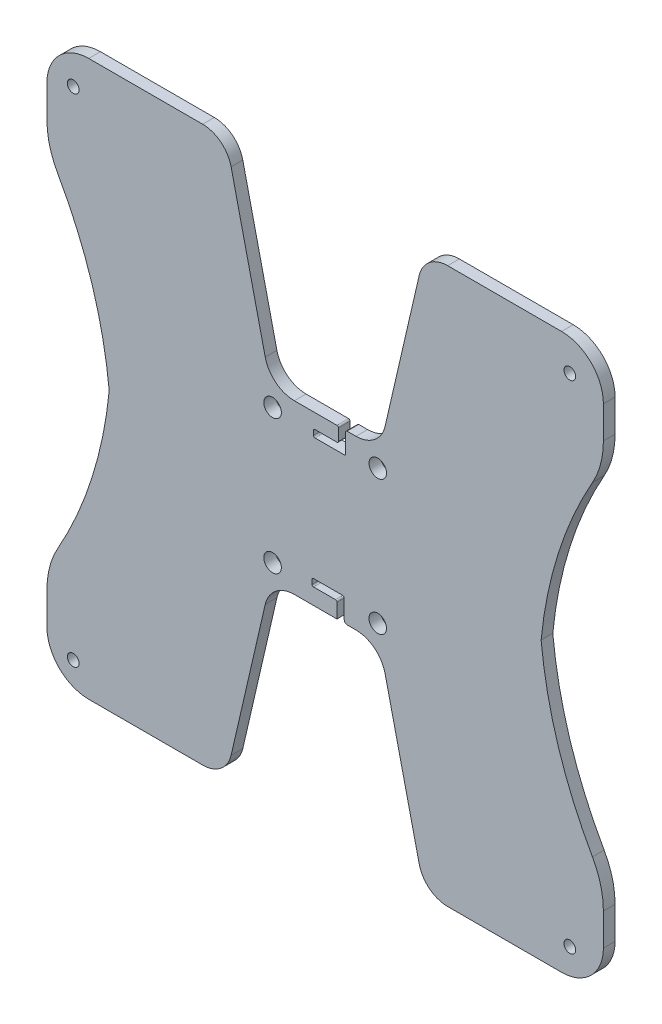
SolidWorks part; units mm, degrees
ref_plane "Front Plane" through (0, 0, 0) normal (0, 0, 1) x (1, 0, 0)
ref_plane "Top Plane" through (0, 0, 0) normal (0, 1, 0) x (1, 0, 0)
ref_plane "Right Plane" through (0, 0, 0) normal (1, 0, 0) x (0, 0, -1)
sketch "Sketch2" plane through (0, 0, 0) normal (0, 0, 1) x (1, 0, 0)
  line L3 (94.3754, -52.7044) -> (94.3754, -56.7044)
  line L4 (93.8754, -57.2044) -> (86.3754, -57.2044)
  line L5 (85.8754, -57.7044) -> (85.8754, -59.2044)
  line L6 (86.3754, -59.7044) -> (96.3754, -59.7044)
  line L7 (96.8754, -59.2044) -> (96.8754, -52.7044)
  line L8 (97.3754, -52.2044) -> (100.3754, -52.2044)
  line L9 (110.3627, -44.2602) -> (122.0425, 6.3307)
  line L10 (131.7862, 14.0812) -> (170.7845, 14.0812)
  line L11 (185.0955, -0.2297) -> (185.0955, -11.2297)
  line L16 (96.3754, -108.6331) -> (96.3754, -102.1331)
  line L17 (95.8754, -101.6331) -> (85.8754, -101.6331)
  line L18 (85.3754, -102.1331) -> (85.3754, -103.6331)
  line L19 (85.8754, -104.1331) -> (93.3754, -104.1331)
  line L20 (93.8754, -104.6331) -> (93.8754, -108.6331)
  line L26 (163.7717, -80.9188) -> (-81.9172, -80.9188) construction
  line L27 (97.3754, -109.6331) -> (100.3754, -109.6331)
  line L28 (185.0955, -161.6078) -> (185.0955, -150.6078)
  line L29 (131.7862, -175.9188) -> (170.7845, -175.9188)
  line L30 (110.3627, -117.5774) -> (122.0425, -168.1683)
  line L31 (185.0955, -161.6078) -> (-5.4045, -161.6078) construction
  line L32 (89.8455, -161.6078) -> (89.8455, -80.9188) construction
  line L33 (82.3155, -52.2044) -> (79.3155, -52.2044)
  line L34 (82.3155, -109.6331) -> (79.3155, -109.6331)
  line L35 (15.9192, -80.9188) -> (261.6081, -80.9188) construction
  line L36 (69.3282, -117.5774) -> (57.6484, -168.1683)
  line L37 (47.9047, -175.9188) -> (8.9064, -175.9188)
  line L38 (-5.4045, -161.6078) -> (-5.4045, -150.6078)
  line L39 (-5.4045, -0.2297) -> (-5.4045, -11.2297)
  line L40 (47.9047, 14.0812) -> (8.9064, 14.0812)
  line L41 (69.3282, -44.2602) -> (57.6484, 6.3307)
  line L42 (82.3155, -52.2044) -> (93.8754, -52.2044)
  line L43 (82.3155, -109.6331) -> (93.8754, -109.6331)
  line L44 (93.8754, -108.6331) -> (93.8754, -109.6331)
  line L45 (142.4554, -175.9188) -> (142.4554, 14.0812) construction
  arc A2 (94.3754, -52.7044) -> (93.8754, -52.2044) centre (93.8754, -52.7044) ccw
  arc A3 (93.8754, -57.2044) -> (94.3754, -56.7044) centre (93.8754, -56.7044) ccw
  arc A5 (85.8754, -59.2044) -> (86.3754, -59.7044) centre (86.3754, -59.2044) ccw
  arc A6 (86.3754, -57.2044) -> (85.8754, -57.7044) centre (86.3754, -57.7044) ccw
  arc A7 (96.3754, -59.7044) -> (96.8754, -59.2044) centre (96.3754, -59.2044) ccw
  arc A8 (97.3754, -52.2044) -> (96.8754, -52.7044) centre (97.3754, -52.7044) ccw
  arc A9 (100.3754, -52.2044) -> (110.3627, -44.2602) centre (100.3754, -41.9544) ccw
  arc A10 (131.7862, 14.0812) -> (122.0425, 6.3307) centre (131.7862, 4.0812) ccw
  arc A11 (185.0955, -0.2297) -> (170.7845, 14.0812) centre (170.7845, -0.2297) ccw
  arc A12 (181.353, -25.4269) -> (185.0955, -11.2297) centre (156.2955, -11.2297) ccw
  arc A13 (181.353, -25.4269) -> (163.7717, -80.9188) centre (303.5955, -94.6875) ccw
  arc A18 (96.3754, -108.6331) -> (97.3754, -109.6331) centre (97.3754, -108.6331) ccw
  arc A19 (96.3754, -102.1331) -> (95.8754, -101.6331) centre (95.8754, -102.1331) ccw
  arc A20 (85.8754, -101.6331) -> (85.3754, -102.1331) centre (85.8754, -102.1331) ccw
  arc A21 (85.3754, -103.6331) -> (85.8754, -104.1331) centre (85.8754, -103.6331) ccw
  arc A22 (93.8754, -104.6331) -> (93.3754, -104.1331) centre (93.3754, -104.6331) ccw
  arc A31 (79.3155, -109.6331) -> (69.3282, -117.5774) centre (79.3155, -119.8831) ccw
  arc A32 (181.353, -136.4106) -> (163.7717, -80.9188) centre (303.5955, -67.15) cw
  arc A33 (181.353, -136.4106) -> (185.0955, -150.6078) centre (156.2955, -150.6078) cw
  arc A34 (185.0955, -161.6078) -> (170.7845, -175.9188) centre (170.7845, -161.6078) cw
  arc A35 (131.7862, -175.9188) -> (122.0425, -168.1683) centre (131.7862, -165.9188) cw
  arc A36 (100.3754, -109.6331) -> (110.3627, -117.5774) centre (100.3754, -119.8831) cw
  arc A37 (47.9047, -175.9188) -> (57.6484, -168.1683) centre (47.9047, -165.9188) ccw
  arc A38 (-5.4045, -161.6078) -> (8.9064, -175.9188) centre (8.9064, -161.6078) ccw
  arc A39 (-1.6621, -136.4106) -> (-5.4045, -150.6078) centre (23.3955, -150.6078) ccw
  arc A40 (-1.6621, -136.4106) -> (15.9192, -80.9188) centre (-123.9045, -67.15) ccw
  arc A41 (-1.6621, -25.4269) -> (15.9192, -80.9188) centre (-123.9045, -94.6875) cw
  arc A42 (-1.6621, -25.4269) -> (-5.4045, -11.2297) centre (23.3955, -11.2297) cw
  arc A43 (-5.4045, -0.2297) -> (8.9064, 14.0812) centre (8.9064, -0.2297) cw
  arc A44 (47.9047, 14.0812) -> (57.6484, 6.3307) centre (47.9047, 4.0812) cw
  arc A45 (79.3155, -52.2044) -> (69.3282, -44.2602) centre (79.3155, -41.9544) cw
  dimension "D6" = 190.5
  dimension "D8" = 1
  dimension "D9" = 1
  dimension "D12" = 1
  dimension "D13" = 1
  dimension "D17" = 1
  dimension "D18" = 1
  dimension "D40" = 2
  dimension "D42" = 1
  dimension "D44" = 1
  dimension "D45" = 1
  dimension "D48" = 1
  dimension "D5" = 190
  dimension "D10" = 7.5
  dimension "D11" = 4
  dimension "D14" = 1.5
  dimension "D15" = 2.5
  dimension "D16" = 10
  dimension "D19" = 6.5
  dimension "D20" = 3
  dimension "D25" = 103
  dimension "D30" = 118.5
  dimension "D41" = 6.5
  dimension "D43" = 10
  dimension "D46" = 1.5
  dimension "D47" = 7.5
  dimension "D49" = 4
extrude "Boss-Extrude1" add sketch "Sketch2" along normal blind 4
sketch "Sketch3" plane through (0, 0, 4) normal (0, 0, 1) x (1, 0, 0)
  line L0 (170.7845, 14.0812) -> (131.7862, 14.0812) construction
  line L1 (-5.4045, -0.2297) -> (-5.4045, -11.2297) construction
  line L2 (8.9064, 14.0812) -> (170.7845, 14.0812) construction
  line L3 (89.8455, 14.0812) -> (89.8455, -175.9188) construction
  line L4 (71.8455, -57.9188) -> (107.8455, -57.9188) construction
  line L5 (8.9064, -175.9188) -> (170.7845, -175.9188) construction
  line L6 (89.8455, -80.9188) -> (119.7664, -80.9188) construction
  circle A0 centre (3.5955, 3.0812) radius 2
  circle A1 centre (3.5955, -166.9188) radius 2
  circle A2 centre (71.8455, -57.9188) radius 3
  circle A3 centre (107.8455, -57.9188) radius 3
  circle A4 centre (71.8455, -103.9188) radius 3
  circle A5 centre (107.8455, -103.9188) radius 3
  circle A6 centre (173.5955, -166.9188) radius 2
  circle A7 centre (173.5955, 3.0812) radius 2
  arc A8 (170.7845, -175.9188) -> (185.0955, -161.6078) centre (170.7845, -161.6078) ccw construction
  point P20 (89.8455, -57.9188)
  dimension "D1" = 170
  dimension "D2" = 23
  dimension "D3" = 170
  dimension "D4" = 11
  dimension "D5" = 36
  dimension "D6" = 46
  dimension "D7" = 9
  dimension "D8" = 6
  dimension "D9" = 6
  dimension "D10" = 6
  dimension "D11" = 6
extrude "Cut-Extrude1" cut sketch "Sketch3" against normal blind 4
ref_plane "Plane1" through (8.9064, 14.0812, 4) normal (-1, 0, 0) x (0, 0, 1)
sketch "Sketch5" plane through (0, 0, 4) normal (0, 0, 1) x (1, 0, 0)
  line L0 (47.9047, 14.0812) -> (8.9064, 14.0812) construction
  line L3 (44.9827, 14.0812) -> (44.9827, -175.9188) construction
  line L4 (8.9064, -175.9188) -> (47.9047, -175.9188) construction
  line L5 (-5.4045, -11.2297) -> (185.0955, -11.2297) construction
